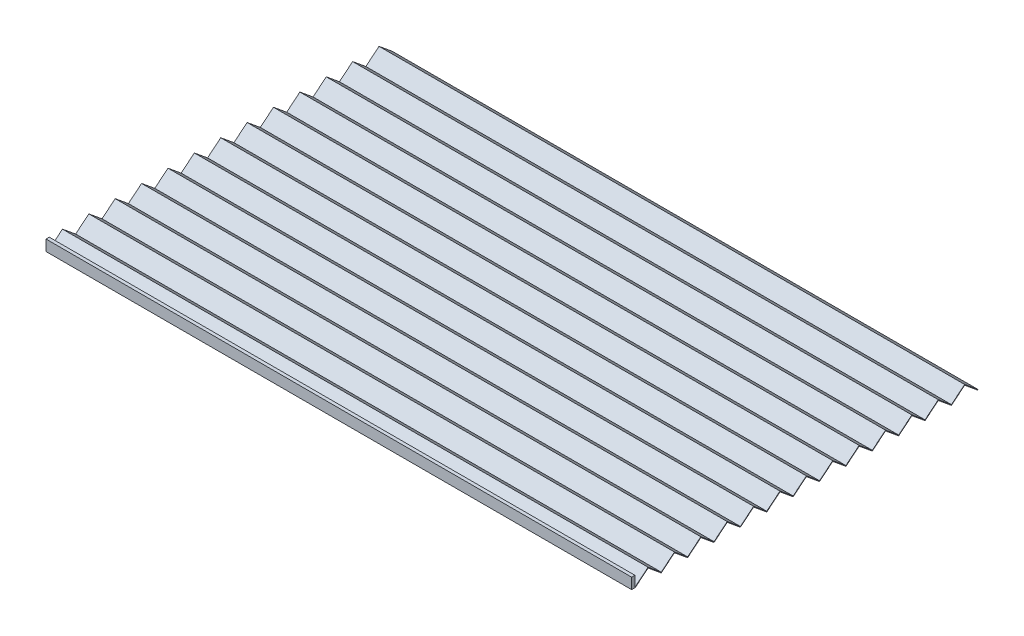
SolidWorks part; units mm, degrees
ref_plane "Front Plane" through (0, 0, 0) normal (0, 0, 1) x (1, 0, 0)
ref_plane "Top Plane" through (0, 0, 0) normal (0, 1, 0) x (1, 0, 0)
ref_plane "Right Plane" through (0, 0, 0) normal (1, 0, 0) x (0, 0, -1)
sketch "Sketch2" plane through (0, 0, 0) normal (0, 0, 1) x (1, 0, 0)
  line L1 (-270, 10) -> (270, 10)
  line L2 (-270, 10) -> (-270, 0)
  line L3 (-270, 0) -> (270, 0)
  line L4 (270, 10) -> (270, 0)
  point P4 (0, 0)
  dimension "D1" = 10
  dimension "D2" = 540
extrude "Boss-Extrude1" add sketch "Sketch2" along normal blind 3
sketch "Sketch3" plane through (270, 0, 0) normal (1, 0, 0) x (0, 0, -1)
  line L0 (0, 10) -> (316.229, 10) construction
  line L1 (0, 0) -> (316.229, 0) construction
  line L2 (316.229, 10) -> (316.229, 0) construction
  line L3 (0, 0) -> (12.1627, 10)
  line L4 (12.1627, 10) -> (24.3253, 0)
  line L5 (24.3253, 0) -> (36.488, 10)
  line L6 (36.488, 10) -> (48.6506, 0)
  line L7 (48.6506, 0) -> (60.8133, 10)
  line L8 (60.8133, 10) -> (72.9759, 0)
  line L9 (72.9759, 0) -> (85.1386, 10)
  line L10 (85.1386, 10) -> (97.3012, 0)
  line L11 (97.3012, 0) -> (109.4639, 10)
  line L12 (109.4639, 10) -> (121.6265, 0)
  line L13 (121.6265, 0) -> (133.7892, 10)
  line L14 (133.7892, 10) -> (145.9518, 0)
  line L15 (145.9518, 0) -> (158.1145, 10)
  line L16 (158.1145, 10) -> (170.2771, 0)
  line L17 (170.2771, 0) -> (182.4398, 10)
  line L18 (182.4398, 10) -> (194.6024, 0)
  line L20 (194.6024, 0) -> (206.7651, 10)
  line L21 (206.7651, 10) -> (218.9277, 0)
  line L22 (218.9277, 0) -> (231.0904, 10)
  line L23 (231.0904, 10) -> (243.2531, 0)
  line L24 (243.2531, 0) -> (255.4157, 10)
  line L25 (255.4157, 10) -> (267.5784, 0)
  line L26 (267.5784, 0) -> (279.741, 10)
  line L27 (279.741, 10) -> (291.9037, 0)
  line L28 (291.9037, 0) -> (304.0663, 10)
  line L29 (304.0663, 10) -> (316.229, 0)
  line L30 (316.229, 10) -> (316.229, 0) construction
extrude "Extrude-Thin1" add sketch "Sketch3" against normal through all thin thin type mid plane wall 0.5
